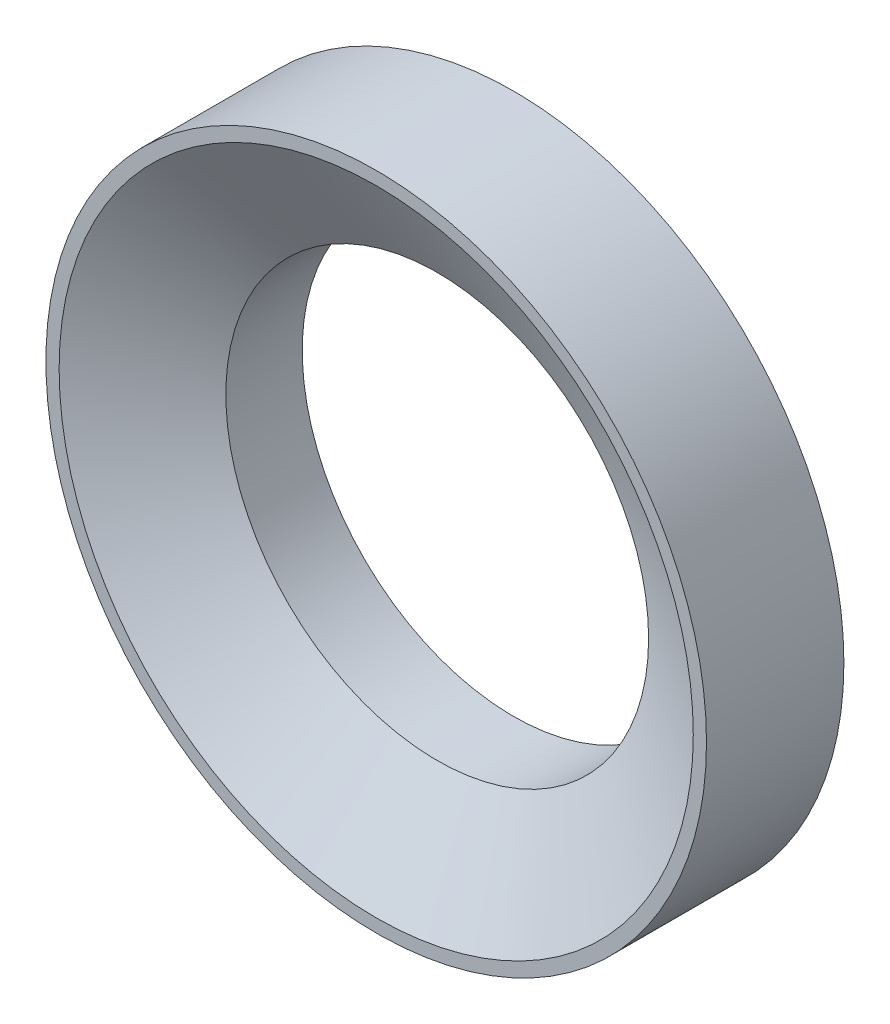
SolidWorks part; units mm, degrees
ref_plane "Front" through (0, 0, 0) normal (0, 0, 1) x (1, 0, 0)
ref_plane "Top" through (0, 0, 0) normal (0, 1, 0) x (1, 0, 0)
ref_plane "Right" through (0, 0, 0) normal (1, 0, 0) x (0, 0, -1)
sketch "Sketch1" plane through (0, 0, 0) normal (-1, 0, 0) x (0, -1, 0)
  line L0 (-4, -2.6) -> (-6.25, -2.6)
  line L1 (-6.25, -2.6) -> (-6.25, 0)
  line L2 (0, 12.9485) -> (0, -19.7339) construction
  line L3 (-4, -2.6) -> (-4, -1.1547)
  line L4 (-6.25, 0) -> (-6, 0)
  line L5 (-6, 0) -> (-4, -1.1547)
  dimension "D1" = 12
  dimension "D0" = 12.5
  dimension "d" = 8
  dimension "h" = 2.6
  dimension "Angle" = 60
revolve "Base-Revolve" add sketch "Sketch1" angle 360 about L2
